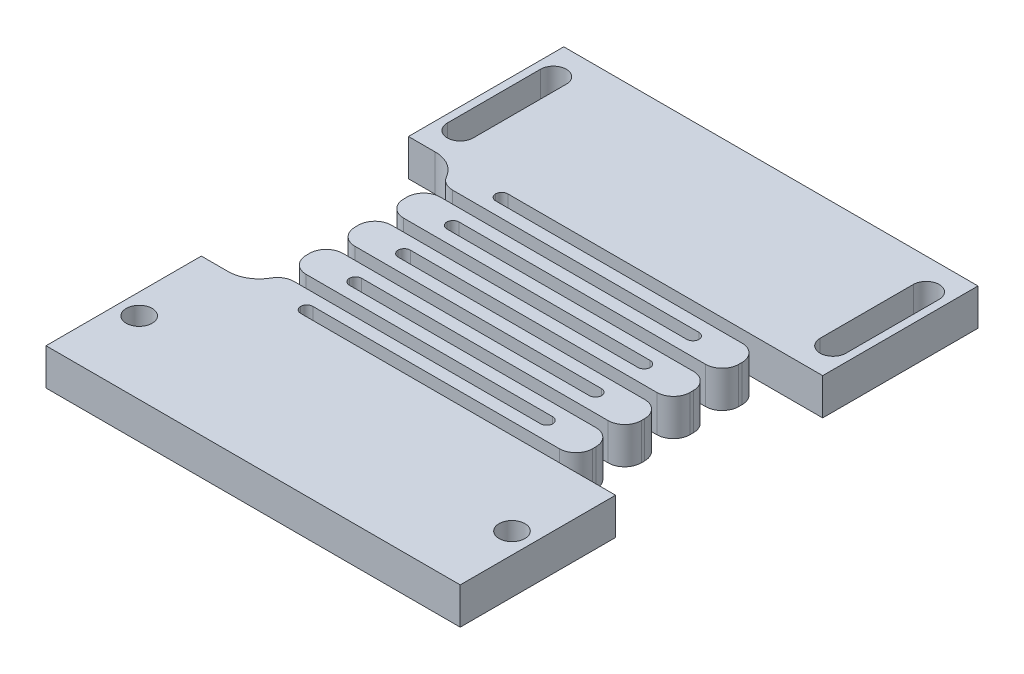
SolidWorks part; units mm, degrees
ref_plane "Front Plane" through (0, 0, 0) normal (0, 0, 1) x (1, 0, 0)
ref_plane "Top Plane" through (0, 0, 0) normal (0, 1, 0) x (1, 0, 0)
ref_plane "Right Plane" through (0, 0, 0) normal (1, 0, 0) x (0, 0, -1)
sketch "Sketch1" plane through (0, 0, 0) normal (0, 1, 0) x (1, 0, 0)
  line L0 (-44.45, 44.45) -> (-6.35, 44.45) construction
  line L1 (-50.8, 63.5) -> (0, 63.5)
  line L2 (-50.8, 63.5) -> (-50.8, 44.45)
  line L3 (-50.8, 0) -> (0, 0)
  line L4 (0, 63.5) -> (0, 44.45)
  line L5 (-50.8, 44.45) -> (-44.45, 44.45)
  line L6 (0, 19.05) -> (0, 0)
  line L7 (-50.8, 19.05) -> (-44.45, 19.05)
  line L8 (-44.45, 44.45) -> (-44.45, 19.05)
  line L9 (0, 19.05) -> (-6.35, 19.05)
  line L11 (0, 44.45) -> (-6.35, 44.45)
  line L12 (-6.35, 19.05) -> (-6.35, 44.45)
  line L13 (-44.45, 19.05) -> (-6.35, 19.05) construction
  line L14 (-50.8, 19.05) -> (-50.8, 0)
  dimension "D1" = 50.8
  dimension "D2" = 63.5
  dimension "D3" = 6.35
  dimension "D4" = 19.05
  dimension "D5" = 19.05
extrude "Boss-Extrude1" add sketch "Sketch1" along normal blind 4.4958
sketch "Sketch3" plane through (0, 4.4958, 0) normal (0, 1, 0) x (1, 0, 0)
  line L0 (-2.54, 0) -> (-2.54, 19.05) construction
  line L1 (-50.8, 0) -> (0, 0) construction
  line L2 (0, 19.05) -> (-6.35, 19.05) construction
  line L3 (-48.26, 0) -> (-48.26, 19.05) construction
  line L4 (-44.45, 19.05) -> (-50.8, 19.05) construction
  line L5 (-50.8, 19.05) -> (-50.8, 0) construction
  line L6 (0, 0) -> (0, 19.05) construction
  line L7 (-48.26, 19.05) -> (-48.26, 63.5) construction
  line L8 (0, 63.5) -> (-50.8, 63.5) construction
  line L9 (-2.54, 19.05) -> (-2.54, 63.5) construction
  line L10 (-48.26, 48.26) -> (-48.26, 59.69) construction
  line L11 (-49.8475, 48.26) -> (-49.8475, 59.69)
  line L12 (-46.6725, 48.26) -> (-46.6725, 59.69)
  line L13 (-2.54, 48.26) -> (-2.54, 59.69) construction
  line L14 (-4.1275, 48.26) -> (-4.1275, 59.69)
  line L15 (-0.9525, 48.26) -> (-0.9525, 59.69)
  line L16 (-48.26, 48.26) -> (-2.54, 48.26) construction
  line L17 (-48.26, 59.69) -> (-2.54, 59.69) construction
  line L18 (-50.8, 44.45) -> (-44.45, 44.45) construction
  circle A0 centre (-48.26, 8.89) radius 1.5875
  circle A1 centre (-2.54, 8.89) radius 1.5875
  arc A2 (-49.8475, 48.26) -> (-46.6725, 48.26) centre (-48.26, 48.26) ccw
  arc A3 (-46.6725, 59.69) -> (-49.8475, 59.69) centre (-48.26, 59.69) ccw
  arc A4 (-4.1275, 48.26) -> (-0.9525, 48.26) centre (-2.54, 48.26) ccw
  arc A5 (-0.9525, 59.69) -> (-4.1275, 59.69) centre (-2.54, 59.69) ccw
  point P24 (-48.26, 53.975)
  point P29 (-2.54, 53.975)
  dimension "D5" = 3.175
  dimension "D6" = 3.175
  dimension "D7" = 1.5875
  dimension "D1" = 2.54
  dimension "D2" = 2.54
  dimension "D3" = 8.89
  dimension "D4" = 8.89
  dimension "D8" = 3.81
  dimension "D9" = 3.81
extrude "Cut-Extrude1" cut sketch "Sketch3" against normal through all both and the other way through all
sketch "Sketch4" plane through (0, 4.4958, 0) normal (0, 1, 0) x (1, 0, 0)
  line L0 (-39.37, 20.5441) -> (-44.45, 20.5441) construction
  line L1 (-44.45, 33.9912) -> (-11.43, 33.9912)
  line L2 (-6.35, 19.05) -> (-6.35, 20.5441)
  line L3 (-44.45, 23.5324) -> (-11.43, 23.5324)
  line L4 (-44.45, 23.5324) -> (-44.45, 22.0382)
  line L5 (-6.35, 20.5441) -> (-39.37, 20.5441)
  line L6 (-44.45, 22.0382) -> (-11.43, 22.0382)
  line L7 (-6.35, 19.05) -> (-39.37, 19.05)
  line L8 (-39.37, 20.5441) -> (-39.37, 19.05)
  line L9 (-44.45, 44.45) -> (-44.45, 19.05) construction
  line L10 (-11.43, 23.5324) -> (-11.43, 22.0382)
  line L11 (-6.35, 25.0265) -> (-39.37, 25.0265)
  line L12 (-6.35, 25.0265) -> (-6.35, 26.5206)
  line L13 (-6.35, 26.5206) -> (-39.37, 26.5206)
  line L14 (-39.37, 25.0265) -> (-39.37, 26.5206)
  line L15 (-11.43, 22.0382) -> (-11.43, 20.5441) construction
  line L16 (-44.45, 28.0147) -> (-11.43, 28.0147)
  line L17 (-44.45, 28.0147) -> (-44.45, 29.5088)
  line L18 (-44.45, 29.5088) -> (-11.43, 29.5088)
  line L19 (-11.43, 28.0147) -> (-11.43, 29.5088)
  line L20 (-6.35, 32.4971) -> (-39.37, 32.4971)
  line L21 (-6.35, 32.4971) -> (-6.35, 31.0029)
  line L22 (-6.35, 31.0029) -> (-39.37, 31.0029)
  line L23 (-39.37, 32.4971) -> (-39.37, 31.0029)
  line L24 (-39.37, 25.0265) -> (-39.37, 23.5324) construction
  line L25 (-11.43, 28.0147) -> (-11.43, 26.5206) construction
  line L26 (-39.37, 31.0029) -> (-39.37, 29.5088) construction
  line L27 (-6.35, 19.05) -> (-6.35, 44.45) construction
  line L28 (-44.45, 35.4853) -> (-11.43, 35.4853)
  line L29 (-11.43, 33.9912) -> (-11.43, 35.4853)
  line L30 (-6.35, 38.4735) -> (-39.37, 38.4735)
  line L31 (-6.35, 38.4735) -> (-6.35, 36.9794)
  line L32 (-6.35, 36.9794) -> (-39.37, 36.9794)
  line L33 (-39.37, 38.4735) -> (-39.37, 36.9794)
  line L34 (-11.43, 33.9912) -> (-11.43, 32.4971) construction
  line L35 (-39.37, 36.9794) -> (-39.37, 35.4853) construction
  line L36 (-44.45, 33.9912) -> (-44.45, 35.4853)
  line L37 (-44.45, 39.9676) -> (-11.43, 39.9676)
  line L38 (-44.45, 41.4618) -> (-11.43, 41.4618)
  line L39 (-11.43, 39.9676) -> (-11.43, 41.4618)
  line L40 (-6.35, 44.45) -> (-39.37, 44.45)
  line L41 (-6.35, 44.45) -> (-6.35, 42.9559)
  line L42 (-6.35, 42.9559) -> (-39.37, 42.9559)
  line L43 (-39.37, 44.45) -> (-39.37, 42.9559)
  line L44 (-39.37, 42.9559) -> (-39.37, 41.4618) construction
  line L45 (-44.45, 39.9676) -> (-44.45, 41.4618)
  line L46 (-11.43, 39.9676) -> (-11.43, 38.4735) construction
  point P16 (0, 0)
  point P27 (0, 0)
  point P43 (0, 0)
  point P45 (-46.0809, 38.3224)
  point P46 (-46.257, 40.0125)
  point P55 (-11.0571, 38.7903)
  point P57 (-7.7286, 50.1043)
  point P58 (-8.8519, 44.2421)
  point P59 (-9.4177, 45.3351)
  dimension "D1" = 5.08
extrude "Cut-Extrude2" cut sketch "Sketch4" against normal through all both and the other way through all
fillet "Fillet1" radius 0.762 18 edges at (-39.37, 2.2479, -32.4971) (-11.43, 2.2479, -22.0382) (-11.43, 2.2479, -23.5324) (-11.43, 2.2479, -29.5088) (-11.43, 2.2479, -28.0147) (-39.37, 2.2479, -25.0265) (-39.37, 2.2479, -31.0029) (-39.37, 2.2479, -26.5206) (-39.37, 2.2479, -20.5441) (-39.37, 2.2479, -19.05) (-39.37, 2.2479, -36.9794) (-39.37, 2.2479, -42.9559) (-39.37, 2.2479, -38.4735) (-39.37, 2.2479, -44.45) (-11.43, 2.2479, -33.9912) (-11.43, 2.2479, -39.9676) (-11.43, 2.2479, -35.4853) (-11.43, 2.2479, -41.4618)
fillet "Fillet2" radius 2.032 16 edges at (-44.45, 2.2479, -22.0382) (-6.35, 2.2479, -20.5441) (-6.35, 2.2479, -25.0265) (-44.45, 2.2479, -23.5324) (-44.45, 2.2479, -28.0147) (-6.35, 2.2479, -26.5206) (-6.35, 2.2479, -31.0029) (-44.45, 2.2479, -29.5088) (-6.35, 2.2479, -42.9559) (-6.35, 2.2479, -38.4735) (-6.35, 2.2479, -36.9794) (-6.35, 2.2479, -32.4971) (-44.45, 2.2479, -41.4618) (-44.45, 2.2479, -39.9676) (-44.45, 2.2479, -35.4853) (-44.45, 2.2479, -33.9912)
fillet "Fillet3" radius 3.81 4 edges at (-44.45, 4.4958, -43.9719) (-44.45, 0, -43.9719) (-44.45, 2.2479, -44.45) (-44.45, 2.2479, -43.4938)
fillet "Fillet4" radius 3.81 4 edges at (-44.45, 2.2479, -19.05) (-44.45, 4.4958, -19.5281) (-44.45, 0, -19.5281) (-44.45, 2.2479, -20.0062)
